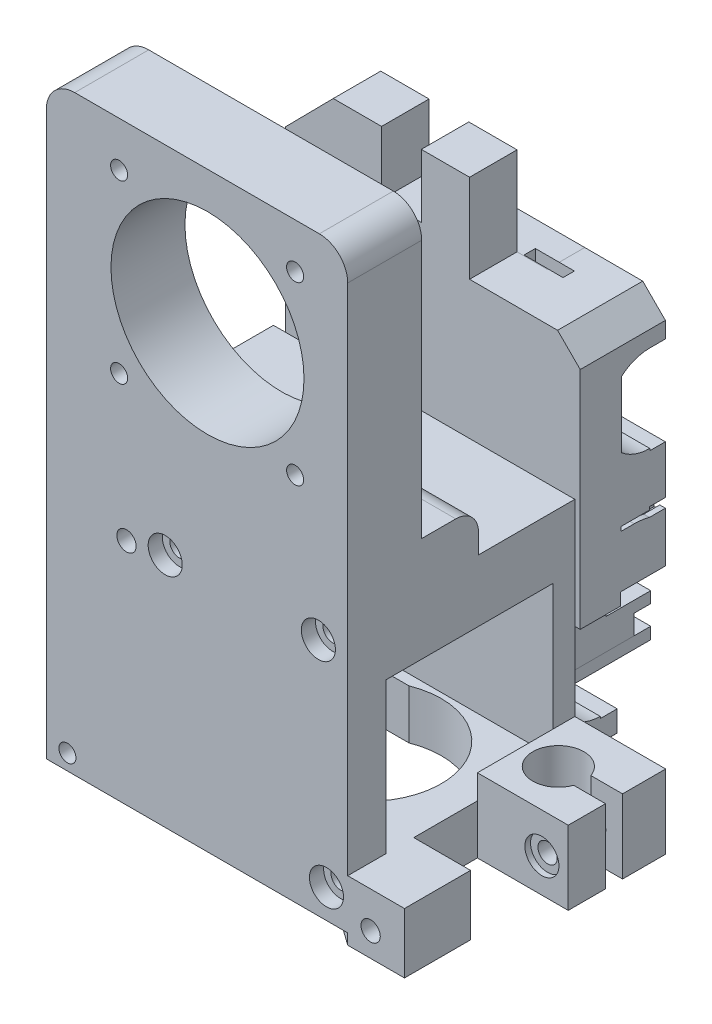
SolidWorks part; units mm, degrees
ref_plane "Front Plane" through (0, 0, 0) normal (0, 0, 1) x (1, 0, 0)
ref_plane "Top Plane" through (0, 0, 0) normal (0, 1, 0) x (1, 0, 0)
ref_plane "Right Plane" through (0, 0, 0) normal (1, 0, 0) x (0, 0, -1)
sketch "Sketch1" plane through (0, 0, 0) normal (0, 0, 1) x (1, 0, 0)
  line L1 (-22.5, 22.5) -> (22.5, 22.5)
  line L2 (-22.5, 22.5) -> (-22.5, -22.5)
  line L3 (-22.5, -22.5) -> (22.5, -22.5)
  line L4 (22.5, 22.5) -> (22.5, -22.5)
  line L5 (-22.5, 22.5) -> (22.5, -22.5) construction
  line L6 (-22.5, -22.5) -> (22.5, 22.5) construction
  point P0 (0, 0)
  dimension "D1" = 45
  dimension "D2" = 45
extrude "Boss-Extrude1" add sketch "Sketch1" along normal blind 35
sketch "Sketch2" plane through (0, 0, 35) normal (0, 0, 1) x (1, 0, 0)
  circle A0 centre (0, 0) radius 13
extrude "Cut-Extrude3" cut sketch "Sketch2" against normal blind 35
sketch "Sketch4" plane through (0, 0, 0) normal (0, 0, -1) x (-1, 0, 0)
  circle A0 centre (-15.8089, 15.9288) radius 1.7
sketch "Sketch5" plane through (0, 0, 0) normal (0, 0, -1) x (-1, 0, 0)
  circle A0 centre (-15.7813, -15.0653) radius 1.7
sketch "Sketch6" plane through (0, 0, 0) normal (0, 0, -1) x (-1, 0, 0)
  circle A0 centre (15.2203, -15.0657) radius 1.7
sketch "Sketch7" plane through (0, 0, 0) normal (0, 0, -1) x (-1, 0, 0)
  circle A0 centre (15.2, 15.9234) radius 1.7
extrude "Cut-Extrude8" cut sketch "Sketch4" against normal blind 35 contours A0
extrude "Cut-Extrude9" cut sketch "Sketch7" against normal blind 35 contours A0
extrude "Cut-Extrude10" cut sketch "Sketch6" against normal blind 35 contours A0
extrude "Cut-Extrude11" cut sketch "Sketch5" against normal blind 35 contours A0
sketch "Sketch8" plane through (22.5, 0, 0) normal (1, 0, 0) x (0, 0, -1)
  line L0 (-4.3639, -12.0361) -> (-35, -12.0361)
  line L2 (-35, -22.5) -> (-35, 22.5) construction
  line L3 (-35, -12.0361) -> (-35, 22.5)
  line L4 (-35, 22.5) -> (-8.4231, 22.5)
  line L5 (-35, 22.5) -> (0, 22.5) construction
  line L6 (-8.4231, 22.5) -> (-8.4231, 12.9255)
  line L7 (-8.4231, 12.9255) -> (-4.3639, 12.9255)
  line L8 (-4.3639, 12.9255) -> (-4.3639, -12.0361)
extrude "Cut-Extrude12" cut sketch "Sketch8" against normal blind 12
sketch "Sketch14" plane through (0, 22.5, 0) normal (0, 1, 0) x (1, 0, 0)
  line L1 (3.1909, -14.7293) -> (9.1909, -14.7293)
  line L2 (3.1909, -14.7293) -> (3.1909, -20.7293)
  line L3 (3.1909, -20.7293) -> (9.1909, -20.7293)
  line L4 (9.1909, -14.7293) -> (9.1909, -20.7293)
  line L5 (3.1909, -14.7293) -> (9.1909, -20.7293) construction
  line L6 (3.1909, -20.7293) -> (9.1909, -14.7293) construction
  point P0 (6.1909, -17.7293)
extrude "Boss-Extrude4" add sketch "Sketch14" along normal blind 2 and the other way blind 37.5
sketch "Sketch20" plane through (0, 24.5, 0) normal (0, 1, 0) x (1, 0, 0)
  line L0 (3.1909, -20.7293) -> (9.1909, -14.7293) construction
  circle A0 centre (6.1909, -17.7293) radius 2.2
  dimension "D1" = 4.4
extrude "Cut-Extrude17" cut sketch "Sketch20" against normal blind 7 and the other way through all contours A0
sketch "Sketch21" plane through (0, 17.5, 0) normal (0, 1, 0) x (1, 0, 0)
  circle A0 centre (6.1909, -17.7293) radius 1.75
extrude "Cut-Extrude18" cut sketch "Sketch21" against normal blind 2
ref_plane "Plane6" through (0, 16.5, 0) normal (0, 1, 0) x (1, 0, 0)
mirror "Mirror6" about plane through (0, 16.5, 0) normal (0, 1, 0) of "Cut-Extrude17"
sketch "Sketch22" plane through (0, -22.5, 0) normal (0, -1, 0) x (1, 0, 0)
  line L1 (-28.0826, 40.0025) -> (25, 40.0025)
  line L2 (-28.0826, 40.0025) -> (-28.0826, 0)
  line L3 (-28.0826, 0) -> (25, 0)
  line L4 (25, 40.0025) -> (25, 0)
  line L5 (-28.0826, 40.0025) -> (25, 0) construction
  line L6 (-28.0826, 0) -> (25, 40.0025) construction
  point P0 (-1.5413, 20.0013)
extrude "Boss-Extrude5" add sketch "Sketch22" along normal blind 44.5712 and the other way blind 1.5626
sketch "Sketch23" plane through (-28.0826, 0, 0) normal (-1, 0, 0) x (0, 0, 1)
  line L1 (3.8043, -58.359) -> (33.254, -58.359)
  line L2 (3.8043, -58.359) -> (3.8043, -31.8415)
  line L3 (3.8043, -31.8415) -> (33.254, -31.8415)
  line L4 (33.254, -58.359) -> (33.254, -31.8415)
  line L5 (3.8043, -58.359) -> (33.254, -31.8415) construction
  line L6 (3.8043, -31.8415) -> (33.254, -58.359) construction
  point P0 (18.5291, -45.1003)
extrude "Cut-Extrude19" cut sketch "Sketch23" against normal through all
sketch "Sketch25" plane through (0, -20.9374, 0) normal (0, 1, 0) x (1, 0, 0)
  circle A0 centre (6.1909, -17.7293) radius 5
extrude "Cut-Extrude24" cut sketch "Sketch25" against normal blind 2.6
sketch "Sketch26" plane through (0, -23.5374, 0) normal (0, 1, 0) x (1, 0, 0)
  circle A0 centre (6.1909, -17.7293) radius 8.1
extrude "Cut-Extrude25" cut sketch "Sketch26" against normal blind 4 contours A0
sketch "Sketch27" plane through (0, -27.5374, 0) normal (0, 1, 0) x (1, 0, 0)
  circle A0 centre (6.1909, -17.7293) radius 6.7
extrude "Cut-Extrude28" cut sketch "Sketch27" against normal blind 6
sketch "Sketch30" plane through (0, -58.359, 0) normal (0, 1, 0) x (1, 0, 0)
  circle A0 centre (6.2079, -17.7293) radius 13
extrude "Cut-Extrude30" cut sketch "Sketch30" against normal blind 10.7676
sketch "Sketch31" plane through (0, -67.0712, 0) normal (0, -1, 0) x (1, 0, 0)
  line L1 (-17.2669, 29.2843) -> (2.0826, 29.2843)
  line L2 (-17.2669, 29.2843) -> (-17.2669, 5.6402)
  line L3 (-17.2669, 5.6402) -> (2.0826, 5.6402)
  line L4 (2.0826, 29.2843) -> (2.0826, 5.6402)
  line L5 (-17.2669, 29.2843) -> (2.0826, 5.6402) construction
  line L6 (-17.2669, 5.6402) -> (2.0826, 29.2843) construction
  point P0 (-7.5922, 17.4622)
extrude "Cut-Extrude31" cut sketch "Sketch31" against normal blind 9.6643
sketch "Sketch34" plane through (-28.0826, 0, 0) normal (-1, 0, 0) x (0, 0, 1)
  circle A4 centre (35.5309, -28.495) radius 1.5
  circle A5 centre (3.5309, -28.495) radius 1.5
  circle A6 centre (35.5309, -60.495) radius 1.5
  circle A7 centre (3.5309, -60.495) radius 1.5
extrude "Cut-Extrude32" cut sketch "Sketch34" against normal blind 9 contours A5 | A7 | A6 | A4
sketch "Sketch37" plane through (25, 0, 0) normal (1, 0, 0) x (0, 0, -1)
  line L1 (-28.3675, -68.9589) -> (-40.0025, -68.9589)
  line L2 (-28.3675, -68.9589) -> (-28.3675, -58.359)
  line L3 (-28.3675, -58.359) -> (-40.0025, -58.359)
  line L4 (-40.0025, -68.9589) -> (-40.0025, -58.359)
  line L5 (-28.3675, -68.9589) -> (-40.0025, -58.359) construction
  line L6 (-28.3675, -58.359) -> (-40.0025, -68.9589) construction
  point P0 (-34.185, -63.659)
extrude "Boss-Extrude6" add sketch "Sketch37" along normal blind 10 and the other way blind 5 draft 29
sketch "Sketch38" plane through (0, 0, 40.0025) normal (0, 0, 1) x (1, 0, 0)
  circle A0 centre (29.0349, -64.7484) radius 1.7
extrude "Cut-Extrude33" cut sketch "Sketch38" against normal blind 10 contours A0
sketch "Sketch39" plane through (0, 0, 40.0025) normal (0, 0, 1) x (1, 0, 0)
  circle A0 centre (-13.9651, -26.7484) radius 1.7
extrude "Cut-Extrude34" cut sketch "Sketch39" against normal through all contours A0
sketch "Sketch40" plane through (25, 0, 0) normal (1, 0, 0) x (0, 0, -1)
  line L0 (0, -67.0712) -> (-28.3675, -67.0712) construction
  line L1 (-17.1599, -54.0712) -> (0, -54.0712)
  line L2 (-17.1599, -54.0712) -> (-17.1599, -67.0712)
  line L3 (-17.1599, -67.0712) -> (0, -67.0712)
  line L4 (0, -54.0712) -> (0, -67.0712)
  line L5 (-17.1599, -54.0712) -> (0, -67.0712) construction
  line L6 (-17.1599, -67.0712) -> (0, -54.0712) construction
  point P0 (-8.5799, -60.5712)
extrude "Boss-Extrude7" add sketch "Sketch40" along normal blind 16 contours L2 L3 L4 L1
sketch "Sketch41" plane through (0, -54.0712, 1.2693) normal (0, 1, 0) x (1, 0, 0)
  circle A0 centre (31.1639, -7.7934) radius 4.5
extrude "Cut-Extrude35" cut sketch "Sketch41" against normal blind 15 contours A0
sketch "Sketch42" plane through (0, -54.0712, 0) normal (0, 1, 0) x (1, 0, 0)
  line L1 (33.5282, -7.5957) -> (42.8596, -7.5957)
  line L2 (33.5282, -7.5957) -> (33.5282, -10.5957)
  line L3 (33.5282, -10.5957) -> (42.8596, -10.5957)
  line L4 (42.8596, -7.5957) -> (42.8596, -10.5957)
  line L5 (33.5282, -7.5957) -> (42.8596, -10.5957) construction
  line L6 (33.5282, -10.5957) -> (42.8596, -7.5957) construction
  point P0 (38.1939, -9.0957)
extrude "Cut-Extrude36" cut sketch "Sketch42" against normal blind 15
sketch "Sketch43" plane through (0, 0, 0) normal (0, 0, -1) x (-1, 0, 0)
  line L1 (-34.6289, -64.4039) -> (-32.7385, -61.0954)
  line L2 (-32.7385, -61.0954) -> (-34.6585, -57.804)
  line L3 (-34.6585, -57.804) -> (-38.4689, -57.821)
  line L4 (-38.4689, -57.821) -> (-40.3594, -61.1295)
  line L5 (-40.3594, -61.1295) -> (-38.4394, -64.421)
  line L6 (-38.4394, -64.421) -> (-34.6289, -64.4039)
  circle A1 centre (-36.5489, -61.1125) radius 3.3 construction
extrude "Cut-Extrude37" cut sketch "Sketch43" against normal blind 5
sketch "Sketch44" plane through (0, 0, 17.1599) normal (0, 0, 1) x (1, 0, 0)
  circle A0 centre (36.3605, -61.0871) radius 1.7
extrude "Cut-Extrude38" cut sketch "Sketch44" against normal blind 23 contours A0
sketch "Sketch48" plane through (0, 0, 0) normal (0, 0, -1) x (-1, 0, 0)
  line L1 (9.0667, -28.8111) -> (10.9572, -25.5026)
  line L2 (10.9572, -25.5026) -> (9.0372, -22.2111)
  line L3 (9.0372, -22.2111) -> (5.2267, -22.2282)
  line L4 (5.2267, -22.2282) -> (3.3362, -25.5367)
  line L5 (3.3362, -25.5367) -> (5.2563, -28.8281)
  line L6 (5.2563, -28.8281) -> (9.0667, -28.8111)
  circle A1 centre (7.1467, -25.5196) radius 3.3 construction
sketch "Sketch49" plane through (0, 0, 0) normal (0, 0, -1) x (-1, 0, 0)
  line L1 (-19.3395, -65.2659) -> (-17.449, -61.9575)
  line L2 (-17.449, -61.9575) -> (-19.369, -58.666)
  line L3 (-19.369, -58.666) -> (-23.1795, -58.6831)
  line L4 (-23.1795, -58.6831) -> (-25.07, -61.9916)
  line L5 (-25.07, -61.9916) -> (-23.15, -65.283)
  line L6 (-23.15, -65.283) -> (-19.3395, -65.2659)
  circle A1 centre (-21.2595, -61.9745) radius 3.3 construction
sketch "Sketch50" plane through (0, 0, 0) normal (0, 0, -1) x (-1, 0, 0)
  line L1 (-17.9116, -28.2435) -> (-16.0212, -24.935)
  line L2 (-16.0212, -24.935) -> (-17.9412, -21.6436)
  line L3 (-17.9412, -21.6436) -> (-21.7517, -21.6606)
  line L4 (-21.7517, -21.6606) -> (-23.6421, -24.9691)
  line L5 (-23.6421, -24.9691) -> (-21.7221, -28.2606)
  line L6 (-21.7221, -28.2606) -> (-17.9116, -28.2435)
  circle A1 centre (-19.8316, -24.9521) radius 3.3 construction
sketch "Sketch51" plane through (0, 0, 40.0025) normal (0, 0, 1) x (1, 0, 0)
  circle A0 centre (-7.1467, -25.5196) radius 1.7
sketch "Sketch52" plane through (0, 0, 40.0025) normal (0, 0, 1) x (1, 0, 0)
  circle A0 centre (19.8316, -24.9521) radius 1.7
sketch "Sketch53" plane through (0, 0, 40.0025) normal (0, 0, 1) x (1, 0, 0)
  circle A0 centre (21.2595, -61.9745) radius 1.7
extrude "Cut-Extrude39" cut sketch "Sketch48" against normal blind 5
extrude "Cut-Extrude40" cut sketch "Sketch49" against normal blind 5
extrude "Cut-Extrude41" cut sketch "Sketch50" against normal blind 5
extrude "Cut-Extrude42" cut sketch "Sketch53" against normal through all contours A0
extrude "Cut-Extrude43" cut sketch "Sketch52" against normal through all contours A0
extrude "Cut-Extrude44" cut sketch "Sketch51" against normal through all
sketch "Sketch55" plane through (0, 0, 0) normal (0, 0, -1) x (-1, 0, 0)
  line L1 (16.7453, -30.1645) -> (18.3136, -26.0487)
  line L2 (18.3136, -26.0487) -> (15.5334, -22.6326)
  line L3 (15.5334, -22.6326) -> (11.1849, -23.3323)
  line L4 (11.1849, -23.3323) -> (9.6166, -27.448)
  line L5 (9.6166, -27.448) -> (12.3967, -30.8642)
  line L6 (12.3967, -30.8642) -> (16.7453, -30.1645)
  circle A0 centre (13.9651, -26.7484) radius 3.8144 construction
extrude "Cut-Extrude46" cut sketch "Sketch55" against normal blind 5
sketch "Sketch57" plane through (0, 0, 40.0025) normal (0, 0, 1) x (1, 0, 0)
  circle A0 centre (-7.1467, -25.5196) radius 3
sketch "Sketch58" plane through (0, 0, 40.0025) normal (0, 0, 1) x (1, 0, 0)
  circle A0 centre (19.8316, -24.9521) radius 3
sketch "Sketch59" plane through (0, 0, 40.0025) normal (0, 0, 1) x (1, 0, 0)
  circle A0 centre (21.2595, -61.9745) radius 3
extrude "Cut-Extrude48" cut sketch "Sketch57" against normal blind 2.5
extrude "Cut-Extrude49" cut sketch "Sketch58" against normal blind 2.5 contours A0
extrude "Cut-Extrude50" cut sketch "Sketch59" against normal blind 2.5 contours A0
sketch "Sketch60" plane through (0, 0, 0) normal (0, 0, -1) x (-1, 0, 0)
  circle A0 centre (-15.8089, 15.9288) radius 3
  circle A1 centre (15.2, 15.9234) radius 3
  circle A2 centre (-15.7813, -15.0653) radius 3
  circle A3 centre (15.2203, -15.0657) radius 3
extrude "Cut-Extrude51" cut sketch "Sketch60" against normal blind 1
sketch "Sketch61" plane through (9.1909, 0, 0) normal (1, 0, 0) x (0, 0, -1)
  line L1 (-21.0836, 7.2178) -> (-14.5415, 7.2178)
  line L2 (-21.0836, 7.2178) -> (-21.0836, -6.8125)
  line L3 (-21.0836, -6.8125) -> (-14.5415, -6.8125)
  line L4 (-14.5415, 7.2178) -> (-14.5415, -6.8125)
  line L5 (-21.0836, 7.2178) -> (-14.5415, -6.8125) construction
  line L6 (-21.0836, -6.8125) -> (-14.5415, 7.2178) construction
  point P0 (-17.8126, 0.2026)
extrude "Cut-Extrude52" cut sketch "Sketch61" against normal blind 6.5 contours L3 L4 L1 L2
sketch "Sketch62" plane through (-22.5, 0, 0) normal (-1, 0, 0) x (0, 0, 1)
  circle A0 centre (9.4038, -7.1271) radius 1.7
sketch "Sketch63" plane through (-22.5, 0, 0) normal (-1, 0, 0) x (0, 0, 1)
  circle A0 centre (29.5162, -7.0688) radius 1.7
sketch "Sketch67" plane through (-22.5, -2.4684, 0) normal (-1, 0, 0) x (0, 0, 1)
  line L1 (26.7141, -1.4425) -> (32.3183, -1.4425)
  line L2 (26.7141, -1.4425) -> (26.7141, -10.4391)
  line L3 (26.7141, -10.4391) -> (32.3183, -10.4391)
  line L4 (32.3183, -1.4425) -> (32.3183, -10.4391)
  line L5 (26.7141, -1.4425) -> (32.3183, -10.4391) construction
  line L6 (26.7141, -10.4391) -> (32.3183, -1.4425) construction
  point P0 (29.5162, -5.9408)
extrude "Boss-Extrude8" add sketch "Sketch67" against normal blind 33
sketch "Sketch68" plane through (-22.5, -2.4684, 0) normal (-1, 0, 0) x (0, 0, 1)
  line L1 (6.6705, -1.2663) -> (12.2748, -1.2663)
  line L2 (6.6705, -1.2663) -> (6.6705, -10.6664)
  line L3 (6.6705, -10.6664) -> (12.2748, -10.6664)
  line L4 (12.2748, -1.2663) -> (12.2748, -10.6664)
  line L5 (6.6705, -1.2663) -> (12.2748, -10.6664) construction
  line L6 (6.6705, -10.6664) -> (12.2748, -1.2663) construction
  point P0 (9.4726, -5.9663)
extrude "Boss-Extrude9" add sketch "Sketch68" against normal blind 33
extrude "Cut-Extrude55" cut sketch "Sketch63" against normal through all contours A0
extrude "Cut-Extrude56" cut sketch "Sketch62" against normal through all contours A0
sketch "Sketch69" plane through (-22.5, 0, 0) normal (-1, 0, 0) x (0, 0, 1)
  circle A0 centre (9.4038, -7.1271) radius 3
  circle A1 centre (29.5162, -7.0688) radius 3
extrude "Cut-Extrude57" cut sketch "Sketch69" against normal blind 2.5
sketch "Sketch70" plane through (0, 0, 28.3675) normal (0, 0, -1) x (-1, 0, 0)
  line L1 (-25.0573, -66.8115) -> (-25.2594, -62.3352)
  line L2 (-25.2594, -62.3352) -> (-29.2371, -60.2722)
  line L3 (-29.2371, -60.2722) -> (-33.0125, -62.6853)
  line L4 (-33.0125, -62.6853) -> (-32.8104, -67.1616)
  line L5 (-32.8104, -67.1616) -> (-28.8328, -69.2246)
  line L6 (-28.8328, -69.2246) -> (-25.0573, -66.8115)
  circle A0 centre (-29.0349, -64.7484) radius 3.8805 construction
extrude "Cut-Extrude58" cut sketch "Sketch70" against normal blind 2.5
sketch "Sketch71" plane through (0, 0, 17.1599) normal (0, 0, 1) x (1, 0, 0)
  circle A0 centre (36.3605, -61.0871) radius 3
extrude "Cut-Extrude59" cut sketch "Sketch71" against normal blind 1 contours A0
sketch "Sketch73" plane through (0, 0, 40.0025) normal (0, 0, 1) x (1, 0, 0)
  circle A0 centre (-24.3693, -64.3228) radius 1.5
extrude "Cut-Extrude61" cut sketch "Sketch73" against normal blind 5
ref_plane "Plane7" through (0, 0, 17.7293) normal (0, 0, 1) x (1, 0, 0)
ref_plane "Plane8" through (0, -20.9374, 0) normal (0, 1, 0) x (1, 0, 0)
sketch "Sketch79" plane through (0, -20.9374, 0) normal (0, 1, 0) x (1, 0, 0)
  line L1 (-52.1, -49.3859) -> (43.5589, -49.3859)
  line L2 (-52.1, -49.3859) -> (-52.1, 1.9049)
  line L3 (-52.1, 1.9049) -> (43.5589, 1.9049)
  line L4 (43.5589, -49.3859) -> (43.5589, 1.9049)
extrude "Cut-Extrude62" cut sketch "Sketch79" along normal blind 59 contours L1 L4 L3 L2
sketch "Sketch80" plane through (0, -20.9374, 0) normal (0, 1, 0) x (1, 0, 0)
  line L1 (25, -40.0025) -> (-28.0826, -40.0025)
  line L2 (25, -40.0025) -> (25, -26.9707)
  line L3 (25, -26.9707) -> (-28.0826, -26.9707)
  line L4 (-28.0826, -40.0025) -> (-28.0826, -26.9707)
  line L5 (25, -40.0025) -> (-28.0826, -26.9707) construction
  line L6 (25, -26.9707) -> (-28.0826, -40.0025) construction
  line L7 (25, 0) -> (25, -40.0025) construction
  line L8 (-28.0826, -40.0025) -> (-28.0826, 0) construction
  line L9 (25, -40.0025) -> (-28.0826, -40.0025) construction
  point P0 (-1.5413, -33.4866)
extrude "Boss-Extrude10" add sketch "Sketch80" along normal blind 58
fillet "Fillet1" radius 5 2 edges at (-28.0826, 37.0626, 33.4866) (25, 37.0626, 33.4866)
sketch "Sketch84" plane through (0, 0, 26.9707) normal (0, 0, -1) x (-1, 0, 0)
  circle A0 centre (-0.299, 13.6036) radius 17
extrude "Cut-Extrude63" cut sketch "Sketch84" against normal blind 22
sketch "Sketch85" plane through (0, 0, 40.0025) normal (0, 0, 1) x (1, 0, 0)
  circle A0 centre (15.7368, 29.1356) radius 1.5
  circle A1 centre (15.7368, -1.8644) radius 1.5
  circle A2 centre (-15.2632, -1.8644) radius 1.5
  circle A3 centre (-15.2632, 29.1356) radius 1.5
extrude "Cut-Extrude64" cut sketch "Sketch85" against normal blind 15
sketch "Sketch86" plane through (0, -20.9374, 0) normal (0, 1, 0) x (1, 0, 0)
  line L0 (25, -26.9707) -> (-28.0826, -26.9707) construction
  line L1 (-28.0826, -26.9707) -> (-14.3865, -26.9707)
  line L2 (-28.0826, -26.9707) -> (-28.0826, -16.9707)
  line L3 (-28.0826, -16.9707) -> (-14.3865, -16.9707)
  line L4 (-14.3865, -26.9707) -> (-14.3865, -16.9707)
extrude "Boss-Extrude11" add sketch "Sketch86" along normal blind 7.5
fillet "Fillet3" radius 3 1 edges at (-21.2346, -13.4374, 16.9707)
sketch "Sketch87" plane through (0, -20.9374, 0) normal (0, 1, 0) x (1, 0, 0)
  line L0 (25, -26.9707) -> (-14.3865, -26.9707) construction
  line L1 (25, -16.9707) -> (14.2343, -16.9707)
  line L2 (25, -16.9707) -> (25, -26.9707)
  line L3 (25, -26.9707) -> (14.2343, -26.9707)
  line L4 (14.2343, -16.9707) -> (14.2343, -26.9707)
  line L5 (-14.3865, -16.9707) -> (-28.0826, -16.9707) construction
  line L6 (25, 0) -> (25, -26.9707) construction
extrude "Boss-Extrude12" add sketch "Sketch87" along normal blind 7.5
sketch "Sketch89" plane through (0, -20.9374, 0) normal (0, 1, 0) x (1, 0, 0)
  line L1 (61.8406, -52.5891) -> (-70.6943, -52.5891)
  line L2 (61.8406, -52.5891) -> (61.8406, 20.0544)
  line L3 (61.8406, 20.0544) -> (-70.6943, 20.0544)
  line L4 (-70.6943, -52.5891) -> (-70.6943, 20.0544)
fillet "Fillet6" radius 4 1 edges at (19.6171, -13.4374, 16.9707)
sketch "Sketch90" plane through (0, 0, 0) normal (0, 0, -1) x (-1, 0, 0)
  line L0 (17.0373, -68.362) -> (17.0373, -50.6891)
  line L1 (14.2497, -71.1901) -> (-14.1775, -71.1901)
  line L2 (25.9937, -36.474) -> (25.9937, 10.3734)
  line L4 (-25.9551, -36.6603) -> (-25.9551, -0.6679)
  line L5 (17.0373, -50.6891) -> (26.0173, -50.6891)
  line L6 (-17.4627, -50.6803) -> (-17.4627, -67.8636)
  line L7 (-17.4627, -50.6803) -> (-23.3678, -50.6803)
  line L8 (-17.4627, -67.8636) -> (-14.1775, -71.1901)
  line L9 (17.0373, -68.362) -> (14.2497, -71.1901)
  line L10 (-23.3678, -50.6803) -> (-23.3627, -48.6193)
  line L11 (-23.3627, -43.1803) -> (-23.3627, -48.6193)
  line L13 (26.0173, -50.6891) -> (26.0173, -40.6819)
  line L14 (26.0173, -40.6819) -> (25.9937, -36.474)
  line L15 (-25.9551, -0.6679) -> (-21.9627, 3.3244)
  line L16 (-21.9627, 3.3244) -> (-6.4627, 3.3557)
  line L17 (-6.4627, 3.3557) -> (-6.4627, 18.9227)
  line L18 (-23.3627, -43.1803) -> (-23.3627, -40.3081)
  line L19 (17.549, 18.9227) -> (25.9937, 10.3734)
  line L20 (2.0414, 18.9227) -> (2.0108, 7.7806)
  line L21 (9.0396, 7.7806) -> (9.0396, 18.9227)
  line L22 (2.0108, 7.7806) -> (9.0396, 7.7806)
  line L23 (2.0414, 18.9227) -> (-6.4627, 18.9227)
  line L24 (9.0396, 18.9227) -> (17.549, 18.9227)
  line L25 (-25.9551, -36.6603) -> (-25.9551, -40.3081)
  line L26 (-25.9551, -40.3081) -> (-23.3627, -40.3081)
extrude "Boss-Extrude13" add sketch "Sketch90" along normal blind 15
ref_plane "Plane9" through (24.9551, 0, 0) normal (1, 0, 0) x (0, 0, -1)
sketch "Sketch93" plane through (24.9551, 0, 0) normal (1, 0, 0) x (0, 0, -1)
  circle A0 centre (12.2562, -11.1714) radius 7.6272
extrude "Cut-Extrude66" cut sketch "Sketch93" against normal blind 49.5
sketch "Sketch94" plane through (25.9551, 0, 0) normal (1, 0, 0) x (0, 0, -1)
  line L0 (7.3045, -5.318) -> (7.3045, -17.0156)
  line L1 (12.2545, -3.5044) -> (16.3704, -3.5044)
  line L2 (16.3704, -4.7037) -> (16.3704, -3.5044)
  line L3 (12.2545, -18.8291) -> (12.2475, -19.1753)
  line L4 (12.2475, -19.1753) -> (15.2475, -19.1908)
  line L5 (15.2475, -19.1908) -> (15.2475, -18.2204)
  arc A0 (7.3045, -17.0156) -> (12.2545, -18.8291) centre (12.2545, -11.1668) ccw
  arc A1 (12.2545, -3.5044) -> (7.3045, -5.318) centre (12.2545, -11.1668) ccw
  arc A2 (15.2475, -18.2204) -> (16.3704, -4.7037) centre (12.2545, -11.1668) ccw
extrude "Cut-Extrude67" cut sketch "Sketch94" against normal blind 53.5
ref_plane "Plane10" through (12.4627, 0, 0) normal (1, 0, 0) x (0, 0, -1)
sketch "Sketch95" plane through (12.4627, 0, 0) normal (1, 0, 0) x (0, 0, -1)
  circle A0 centre (12.0924, -56.1751) radius 7.6764
extrude "Cut-Extrude68" cut sketch "Sketch95" against normal blind 25.2
sketch "Sketch96" plane through (17.4627, 0, 0) normal (1, 0, 0) x (0, 0, -1)
  line L0 (7.0266, -61.9445) -> (7.0939, -50.6803)
  line L1 (7.0939, -50.6803) -> (18.0396, -50.6803)
  line L3 (12.0174, -63.8278) -> (12.0174, -64.1642)
  line L4 (12.0174, -64.1642) -> (15, -64.1642)
  line L5 (15, -50.6803) -> (15, -67.8636) construction
  line L6 (15, -64.1642) -> (15, -63.2948)
  arc A0 (7.0266, -61.9445) -> (12.0174, -63.8278) centre (12.1456, -55.9335) ccw
  arc A1 (15, -63.2948) -> (18.0396, -50.6803) centre (12.1456, -55.9335) ccw
extrude "Cut-Extrude69" cut sketch "Sketch96" against normal blind 34.5
sketch "Sketch98" plane through (23.3627, 0, 0) normal (1, 0, 0) x (0, 0, -1)
  line L1 (7.1104, -43.1905) -> (15.1235, -43.1905)
  line L2 (7.1104, -43.1905) -> (7.1104, -38.1356)
  line L3 (7.1104, -38.1356) -> (15.1235, -38.1356)
  line L4 (15.1235, -43.1905) -> (15.1235, -38.1356)
extrude "Cut-Extrude70" cut sketch "Sketch98" against normal through all both and the other way through all
sketch "Sketch99" plane through (23.3627, 0, 0) normal (1, 0, 0) x (0, 0, -1)
  line L1 (15, -48.6193) -> (12.1018, -48.6193)
  line L2 (15, -48.6193) -> (15, -45.1749)
  line L3 (15, -45.1749) -> (12.1018, -45.1749)
  line L4 (12.1018, -48.6193) -> (12.1018, -45.1749)
extrude "Cut-Extrude71" cut sketch "Sketch99" against normal blind 49.5
sketch "Sketch100" plane through (0, 0, -15) normal (0, 0, -1) x (-1, 0, 0)
  line L0 (-25.9551, -28.9452) -> (-24.9628, -28.9452)
  line L1 (-25.9551, -19.1895) -> (-25.9551, -38.1356) construction
  line L2 (-24.9628, -28.9452) -> (-24.9628, -29.6536)
  line L3 (-24.9628, -29.6536) -> (-23.9626, -29.6536)
  line L4 (-23.9626, -29.6536) -> (-23.9626, -28.9452)
  line L5 (-23.9626, -28.9452) -> (-22.9642, -28.9452)
  line L6 (-22.9642, -28.9452) -> (-22.9586, -29.6536)
  line L7 (-22.9586, -29.6536) -> (-21.963, -29.6536)
  line L8 (-21.963, -29.6536) -> (-21.963, -28.9452)
  line L9 (-21.963, -28.9452) -> (-20.9649, -28.9452)
  line L10 (-20.9649, -28.9452) -> (-20.9593, -29.6526)
  line L11 (-20.9593, -29.6526) -> (-19.966, -29.6447)
  line L12 (-19.966, -29.6447) -> (-19.9723, -28.852)
  line L13 (-19.9723, -28.852) -> (-19.3112, -28.5436)
  line L14 (-19.3112, -28.5436) -> (-19.0086, -29.1925)
  line L15 (-19.0086, -29.1925) -> (-18.1014, -28.7694)
  line L16 (-18.1014, -28.7694) -> (-18.4041, -28.1205)
  line L17 (-18.4041, -28.1205) -> (-17.5043, -27.7008)
  line L18 (-17.5043, -27.7008) -> (-17.2016, -28.3497)
  line L19 (-17.2016, -28.3497) -> (-16.2902, -27.9246)
  line L20 (-16.2902, -27.9246) -> (-16.5928, -27.2757)
  line L21 (-16.5928, -27.2757) -> (-15.6945, -26.8567)
  line L22 (-15.6945, -26.8567) -> (-15.2198, -27.8743)
  line L23 (-15.2198, -27.8743) -> (-14.3102, -27.4501)
  line L24 (-14.3102, -27.4501) -> (-14.7283, -26.5536)
  line L25 (-14.7283, -26.5536) -> (-13.7535, -26.5536)
  line L26 (-13.7535, -26.5536) -> (-13.7535, -27.2739)
  line L27 (-13.7535, -27.2739) -> (-12.7588, -27.2739)
  line L28 (-12.7588, -27.2739) -> (-12.7588, -26.5536)
  line L29 (-12.7588, -26.5536) -> (-11.7545, -26.5536)
  line L30 (-11.7545, -26.5536) -> (-11.7545, -27.2739)
  line L31 (-11.7545, -27.2739) -> (-10.7569, -27.2739)
  line L32 (-10.7569, -27.2739) -> (-10.7569, -26.5536)
  line L33 (-10.7569, -26.5536) -> (-9.7531, -26.5536)
  line L34 (-9.7531, -26.5536) -> (-9.7531, -27.2739)
  line L35 (-9.7531, -27.2739) -> (-8.7561, -27.2739)
  line L36 (-8.7561, -27.2739) -> (-8.7561, -26.5536)
  line L37 (-8.7561, -26.5536) -> (-7.7518, -26.5536)
  line L38 (-7.7518, -26.5536) -> (-7.7518, -27.2739)
  line L39 (-7.7518, -27.2739) -> (-7.4588, -27.2739)
  line L40 (-7.4588, -27.2739) -> (-6.7129, -27.7765)
  line L41 (-6.7129, -27.7765) -> (-6.455, -27.9003)
  line L42 (-6.455, -27.9003) -> (-6.8083, -25.7675)
  line L43 (-6.8083, -25.7675) -> (-15.08, -25.7675)
  line L44 (-15.08, -25.7675) -> (-20.1972, -28.16)
  line L45 (-20.1972, -28.16) -> (-25.9551, -28.1993)
  line L46 (-25.9551, -28.1993) -> (-25.9551, -28.9452)
sketch "Sketch104" plane through (0, 0, -15) normal (0, 0, -1) x (-1, 0, 0)
  line L0 (-25.9627, -29.3147) -> (-24.9628, -29.3147)
  line L1 (-24.9628, -28.9452) -> (-24.9628, -29.6536) construction
  line L2 (-24.9628, -29.3147) -> (-24.9627, -30.0666)
  line L3 (-24.9627, -30.0666) -> (-23.9627, -30.0666)
  line L4 (-23.9627, -30.0666) -> (-23.9626, -29.2994)
  line L5 (-23.9626, -29.6536) -> (-23.9626, -28.9452) construction
  line L6 (-23.9626, -29.2994) -> (-22.9614, -29.2994)
  line L7 (-22.9642, -28.9452) -> (-22.9586, -29.6536) construction
  line L8 (-22.9614, -29.2994) -> (-22.9627, -30.0666)
  line L9 (-22.9627, -30.0666) -> (-21.9627, -30.0666)
  line L10 (-21.9627, -30.0666) -> (-21.9627, -29.3147)
  line L11 (-21.9627, -29.3147) -> (-20.9627, -29.3147)
  line L12 (-20.9627, -29.3147) -> (-20.9627, -30.0666)
  line L13 (-20.9627, -30.0666) -> (-19.9627, -30.0666)
  line L14 (-19.9627, -30.0666) -> (-19.9627, -29.3)
  line L15 (-19.9627, -29.3) -> (-19.1441, -28.9183)
  line L16 (-19.1441, -28.9183) -> (-18.8263, -29.5997)
  line L17 (-18.8263, -29.5997) -> (-17.92, -29.1771)
  line L18 (-17.92, -29.1771) -> (-18.2378, -28.4956)
  line L19 (-18.2378, -28.4956) -> (-17.3315, -28.073)
  line L20 (-17.3315, -28.073) -> (-17.0137, -28.7545)
  line L21 (-17.0137, -28.7545) -> (-16.1074, -28.3318)
  line L22 (-16.1074, -28.3318) -> (-16.4252, -27.6504)
  line L23 (-16.4252, -27.6504) -> (-15.5188, -27.2278)
  line L24 (-15.5188, -27.2278) -> (-15.2011, -27.9092)
  line L25 (-15.2011, -27.9092) -> (-14.2948, -27.4866)
  line L26 (-14.2948, -27.4866) -> (-14.5521, -26.9347)
  line L27 (-14.5521, -26.9347) -> (-13.7627, -26.9347)
  line L28 (-13.7627, -26.9347) -> (-13.7627, -27.6866)
  line L29 (-13.7627, -27.6866) -> (-12.7627, -27.6866)
  line L30 (-12.7627, -27.6866) -> (-12.7588, -26.9137)
  line L31 (-12.7588, -27.2739) -> (-12.7588, -26.5536) construction
  line L32 (-12.7588, -26.9137) -> (-11.7627, -26.9347)
  line L33 (-11.7627, -26.9347) -> (-11.7627, -27.6866)
  line L34 (-11.7627, -27.6866) -> (-10.7627, -27.6866)
  line L35 (-10.7627, -27.6866) -> (-10.7627, -26.9347)
  line L36 (-10.7627, -26.9347) -> (-9.7627, -26.9347)
  line L37 (-9.7627, -26.9347) -> (-9.7627, -27.6866)
  line L38 (-9.7627, -27.6866) -> (-8.7627, -27.6866)
  line L39 (-8.7627, -27.6866) -> (-8.7627, -26.9347)
  line L40 (-8.7627, -26.9347) -> (-7.7627, -26.9347)
  line L41 (-7.7627, -26.9347) -> (-7.7627, -27.6866)
  line L42 (-7.7627, -27.6866) -> (-6.8547, -27.6866)
  line L43 (-6.8547, -27.6866) -> (-6.8367, -25.2817)
  line L44 (-6.8367, -25.2817) -> (-6.8381, -25.2833)
  line L45 (-6.8381, -25.2833) -> (-15.2958, -25.3392)
  line L46 (-15.2958, -25.3392) -> (-20.3315, -27.6866)
  line L47 (-20.3315, -27.6866) -> (-25.9551, -27.6866)
  line L48 (-25.9551, -19.1895) -> (-25.9551, -38.1356) construction
  line L49 (-25.9551, -27.6866) -> (-25.9627, -29.3147)
extrude "Cut-Extrude75" cut sketch "Sketch104" against normal blind 2.8
extrude "Cut-Extrude76" cut sketch "Sketch100" against normal blind 7.8
ref_plane "Plane11" through (25.9551, -29.3147, -12.2) normal (-1, 0, 0) x (0, 0, 1)
fillet "Fillet9" radius 10 1 edges at (25.4589, -28.9452, -12.2)
sketch "Sketch107" plane through (0, 0, -15) normal (0, 0, -1) x (-1, 0, 0)
  line L0 (8.6873, -27.1166) -> (8.6873, -26.3647)
  line L1 (8.6873, -26.3647) -> (9.6873, -26.3647)
  line L2 (9.6873, -26.3647) -> (9.6873, -27.1166)
  line L3 (9.6873, -27.1166) -> (10.6873, -27.1166)
  line L4 (10.6873, -27.1166) -> (10.6873, -26.3647)
  line L5 (10.6873, -26.3647) -> (11.3006, -26.3647)
  line L6 (11.3006, -26.3647) -> (11.5044, -26.4824)
  line L7 (11.5044, -26.4824) -> (11.1285, -27.1335)
  line L8 (11.1285, -27.1335) -> (11.9945, -27.6335)
  line L9 (11.9945, -27.6335) -> (12.3705, -26.9824)
  line L10 (12.3705, -26.9824) -> (13.2365, -27.4824)
  line L11 (13.2365, -27.4824) -> (12.8606, -28.1335)
  line L12 (12.8606, -28.1335) -> (13.7266, -28.6335)
  line L13 (13.7266, -28.6335) -> (14.1025, -27.9824)
  line L14 (14.1025, -27.9824) -> (14.9685, -28.4824)
  line L15 (14.9685, -28.4824) -> (14.5926, -29.1335)
  line L16 (14.5926, -29.1335) -> (15.4586, -29.6335)
  line L17 (15.4586, -29.6335) -> (15.8346, -28.9824)
  line L18 (15.8346, -28.9824) -> (16.7006, -29.4824)
  line L19 (16.7006, -29.4824) -> (16.3247, -30.1335)
  line L20 (16.3247, -30.1335) -> (17.1907, -30.6335)
  line L21 (17.1907, -30.6335) -> (17.5666, -29.9824)
  line L22 (17.5666, -29.9824) -> (18.4326, -30.4824)
  line L23 (18.4326, -30.4824) -> (18.0567, -31.1335)
  line L24 (18.0567, -31.1335) -> (18.9227, -31.6335)
  line L25 (18.9227, -31.6335) -> (19.2987, -30.9824)
  line L26 (19.2987, -30.9824) -> (20.0373, -31.4088)
  line L27 (20.0373, -31.4088) -> (20.0373, -32.0665)
  line L28 (20.0373, -32.0665) -> (21.0373, -32.0665)
  line L29 (21.0373, -32.0665) -> (21.0373, -31.3147)
  line L30 (21.0373, -31.3147) -> (22.0373, -31.3147)
  line L31 (22.0373, -31.3147) -> (22.0373, -32.0665)
  line L32 (22.0373, -32.0665) -> (23.0373, -32.0665)
  line L33 (23.0373, -32.0665) -> (23.0373, -31.3147)
  line L34 (23.0373, -31.3147) -> (24.0373, -31.3147)
  line L35 (24.0373, -31.3147) -> (24.0373, -32.0665)
  line L36 (24.0373, -32.0665) -> (25.0373, -32.0665)
  line L37 (25.0373, -32.0665) -> (25.0373, -31.3079)
  line L38 (25.0373, -31.3079) -> (26.0373, -31.3147)
  line L39 (26.0373, -31.3147) -> (25.9937, -30.1821)
  line L40 (25.9937, -36.474) -> (25.9937, -19.1895) construction
  line L41 (25.9937, -30.1821) -> (20.1665, -30.1821)
  line L42 (20.1665, -30.1821) -> (11.5852, -25.2668)
  line L43 (11.5852, -25.2668) -> (8.2237, -25.2255)
  line L44 (8.2237, -25.2255) -> (7.9365, -27.1166)
  line L45 (7.9365, -27.1166) -> (8.6873, -27.1166)
sketch "Sketch108" plane through (0, 0, -15) normal (0, 0, -1) x (-1, 0, 0)
  line L0 (8.2264, -26.6999) -> (8.6587, -26.7322)
  line L1 (8.6587, -26.7322) -> (8.6587, -25.9627)
  line L2 (8.6587, -25.9627) -> (9.6644, -25.9627)
  line L3 (9.6644, -25.9627) -> (9.6873, -26.6994)
  line L4 (9.6873, -26.6994) -> (10.6873, -26.6994)
  line L5 (10.6873, -26.6994) -> (10.6873, -25.9627)
  line L6 (10.6873, -25.9627) -> (11.4044, -25.9627)
  line L7 (11.4044, -25.9627) -> (11.7067, -26.1175)
  line L8 (11.7067, -26.1175) -> (11.3604, -26.7935)
  line L9 (11.3604, -26.7935) -> (12.1825, -27.308)
  line L10 (11.9945, -27.6335) -> (12.3705, -26.9824) construction
  line L11 (12.1825, -27.308) -> (12.5588, -26.6562)
  line L12 (12.5588, -26.6562) -> (13.4099, -27.1477)
  line L13 (13.4099, -27.1477) -> (13.0485, -27.808)
  line L14 (13.2365, -27.4824) -> (12.8606, -28.1335) construction
  line L15 (13.0485, -27.808) -> (13.9146, -28.3079)
  line L16 (13.7266, -28.6335) -> (14.1025, -27.9824) construction
  line L17 (13.9146, -28.3079) -> (14.3024, -27.6361)
  line L18 (14.3024, -27.6361) -> (15.1639, -28.1335)
  line L19 (15.1639, -28.1335) -> (14.7806, -28.8079)
  line L20 (14.7806, -28.8079) -> (15.6466, -29.308)
  line L21 (15.4586, -29.6335) -> (15.8346, -28.9824) construction
  line L22 (15.6466, -29.308) -> (16.0379, -28.6302)
  line L23 (16.0379, -28.6302) -> (16.9035, -29.13)
  line L24 (16.9035, -29.13) -> (16.5126, -29.8079)
  line L25 (16.7006, -29.4824) -> (16.3247, -30.1335) construction
  line L26 (16.5126, -29.8079) -> (17.3362, -30.2827)
  line L27 (17.3362, -30.2827) -> (17.7516, -29.6189)
  line L28 (17.7516, -29.6189) -> (18.6251, -30.1225)
  line L29 (18.6251, -30.1225) -> (18.2561, -30.7733)
  line L30 (18.2561, -30.7733) -> (19.1107, -31.2666)
  line L31 (19.1107, -31.2666) -> (19.485, -30.6183)
  line L32 (19.485, -30.6183) -> (20.0465, -30.9425)
  line L33 (20.0465, -30.9425) -> (20.0444, -31.6493)
  line L34 (20.0444, -31.6493) -> (21.0373, -31.6493)
  line L35 (21.0373, -31.6493) -> (21.0373, -30.8966)
  line L36 (21.0373, -30.8966) -> (22.0388, -30.8966)
  line L37 (22.0388, -30.8966) -> (22.0373, -31.6493)
  line L38 (22.0373, -31.3147) -> (22.0373, -32.0665) construction
  line L39 (22.0373, -31.6493) -> (23.0373, -31.6493)
  line L40 (23.0373, -32.0665) -> (23.0373, -31.3147) construction
  line L41 (23.0373, -31.6493) -> (23.0373, -30.8966)
  line L42 (23.0373, -30.8966) -> (24.0311, -30.8966)
  line L43 (24.0311, -30.8966) -> (24.0373, -31.6493)
  line L44 (24.0373, -31.6493) -> (25.0373, -31.6493)
  line L45 (25.0373, -32.0665) -> (25.0373, -31.3079) construction
  line L46 (25.0373, -31.6493) -> (25.0373, -30.8966)
  line L47 (25.0373, -30.8966) -> (26.0373, -30.9121)
  line L48 (26.0373, -30.9121) -> (25.9937, -29.6617)
  line L49 (25.9937, -36.474) -> (25.9937, -19.1895) construction
  line L50 (25.9937, -29.6617) -> (20.0843, -29.6617)
  line L51 (20.0843, -29.6617) -> (11.5106, -24.7117)
  line L52 (11.5106, -24.7117) -> (7.7353, -24.6752)
  line L53 (7.7353, -24.6752) -> (8.2264, -26.6999)
extrude "Cut-Extrude77" cut sketch "Sketch107" against normal blind 2.8
extrude "Cut-Extrude78" cut sketch "Sketch108" against normal blind 7.8
sketch "Sketch109" plane through (0, 0, -15) normal (0, 0, -1) x (-1, 0, 0)
  line L5 (19.305, -0.4593) -> (22.7798, -0.4593)
  line L6 (19.305, -0.4593) -> (19.305, -2.2282)
  line L7 (19.305, -2.2282) -> (22.7798, -2.2282)
  line L8 (22.7798, -0.4593) -> (22.7798, -2.2282)
ref_plane "Plane12" through (-20.9937, 0, 0) normal (-1, 0, 0) x (0, 0, 1)
sketch "Sketch111" plane through (-20.9937, 0, 0) normal (-1, 0, 0) x (0, 0, 1)
  circle A0 centre (-11.5069, -11.1119) radius 9.9738
sweep "Cut-Sweep2" cut profiles "Sketch109" path "Sketch111"
sketch "Sketch112" plane through (0, 0, -15) normal (0, 0, -1) x (-1, 0, 0)
  line L1 (-20.7374, -0.4219) -> (-17.1806, -0.4219)
  line L2 (-20.7374, -0.4219) -> (-20.7374, -2.2289)
  line L3 (-20.7374, -2.2289) -> (-17.1806, -2.2289)
  line L4 (-17.1806, -0.4219) -> (-17.1806, -2.2289)
ref_plane "Plane13" through (18.9551, 0, 0) normal (1, 0, 0) x (0, 0, -1)
sketch "Sketch113" plane through (18.9551, 0, 0) normal (1, 0, 0) x (0, 0, -1)
  circle A0 centre (13.3305, -11.1949) radius 9.8876
sweep "Cut-Sweep3" cut profiles "Sketch112" path "Sketch113"
ref_plane "Plane14" through (0, 0, -9.5) normal (0, 0, -1) x (-1, 0, 0)
sketch "Sketch115" plane through (0, 0, -9.5) normal (0, 0, -1) x (-1, 0, 0)
  line L0 (-14.4186, -0.1631) -> (-14.4186, 4.2277)
  line L4 (-14.4186, -0.1631) -> (-12.7002, -3.1395)
  line L5 (-12.7002, -3.1395) -> (-9.2633, -3.1395)
  line L6 (-9.2633, -3.1395) -> (-7.5449, -0.1631)
  line L10 (9.0279, -0.1631) -> (10.7492, -3.1445)
  line L11 (10.7492, -3.1445) -> (14.1918, -3.1445)
  line L12 (14.1918, -3.1445) -> (15.9131, -0.1631)
  line L13 (-7.5449, -0.1631) -> (-7.5449, 4.6855)
  line L14 (9.0279, -0.1631) -> (9.0279, 4.05)
  line L15 (15.9131, -0.1631) -> (15.9131, 4.3954)
  line L20 (-14.4186, 4.2277) -> (-7.5449, 4.6855)
  line L21 (10.7492, 2.8183) -> (9.8886, 1.3276) [skipped]
  line L22 (15.9131, -0.1631) -> (15.0525, 1.3276) [skipped]
  line L23 (-12.7002, 2.8133) -> (-13.5594, 1.3251) [skipped]
  line L24 (-7.5449, -0.1631) -> (-8.4041, 1.3251) [skipped]
  line L25 (15.9131, 4.3954) -> (9.0279, 4.05)
  line L27 (-9.2633, 2.8133) -> (-10.9817, 2.8133) [skipped]
  line L28 (14.1918, 2.8183) -> (12.4705, 2.8183) [skipped]
  circle A0 centre (-10.9817, -0.1631) radius 2.5 construction
  circle A1 centre (12.4705, -0.1631) radius 2.5 construction
  dimension "D1" = 5
  dimension "D2" = 5
extrude "Cut-Extrude79" cut sketch "Sketch115" against normal mid plane 2
sketch "Sketch116" plane through (-25.9937, 0, 0) normal (-1, 0, 0) x (0, 0, 1)
  line L1 (-8.3638, 3.345) -> (-19.7477, 3.345)
  line L2 (-8.3638, 3.345) -> (-8.3638, 20.7304)
  line L3 (-8.3638, 20.7304) -> (-19.7477, 20.7304)
  line L4 (-19.7477, 3.345) -> (-19.7477, 20.7304)
extrude "Cut-Extrude80" cut sketch "Sketch116" against normal blind 64
ref_plane "Plane15" through (0, 0, -11.2) normal (0, 0, -1) x (-1, 0, 0)
sketch "Sketch117" plane through (0, 0, -11.2) normal (0, 0, -1) x (-1, 0, 0)
  line L0 (-12.8024, -67.142) -> (-12.8024, -62.5486)
  line L1 (-8.4723, -69.642) -> (-7.0289, -67.142)
  line L5 (-12.8024, -67.142) -> (-11.359, -69.642)
  line L6 (-11.359, -69.642) -> (-8.4723, -69.642)
  line L7 (11.4583, -69.6854) -> (12.9017, -67.1854)
  line L11 (7.1282, -67.1854) -> (8.5716, -69.6854)
  line L12 (8.5716, -69.6854) -> (11.4583, -69.6854)
  line L13 (-7.0289, -67.142) -> (-6.8957, -62.5486)
  line L14 (-12.8024, -62.5486) -> (-6.8957, -62.5486)
  line L15 (7.1282, -67.1854) -> (7.1282, -62.6875)
  line L16 (7.1282, -62.6875) -> (12.9017, -62.6875)
  line L17 (12.9017, -62.6875) -> (12.9017, -67.1854)
  line L19 (8.5716, -64.6854) -> (7.8499, -65.9354) [skipped]
  line L20 (12.9017, -67.1854) -> (12.18, -65.9354) [skipped]
  line L21 (10.015, -64.6854) -> (8.5716, -64.6854) [skipped]
  line L22 (-8.4723, -64.642) -> (-9.9157, -64.642) [skipped]
  line L23 (-7.0289, -67.142) -> (-7.7506, -65.892) [skipped]
  line L24 (-12.0807, -65.892) -> (-12.8024, -67.142) [skipped]
  circle A0 centre (-9.9157, -67.142) radius 2.5 construction
  circle A1 centre (10.015, -67.1854) radius 2.5 construction
  dimension "D1" = 5
  dimension "D2" = 5
extrude "Cut-Extrude81" cut sketch "Sketch117" against normal mid plane 2
sketch "Sketch118" plane through (0, 0, 17.7293) normal (0, 0, 1) x (1, 0, 0)
  line L1 (84.2875, 52.3773) -> (-70.9583, 52.3773)
  line L2 (84.2875, 52.3773) -> (84.2875, -85.5503)
  line L3 (84.2875, -85.5503) -> (-70.9583, -85.5503)
  line L4 (-70.9583, 52.3773) -> (-70.9583, -85.5503)
